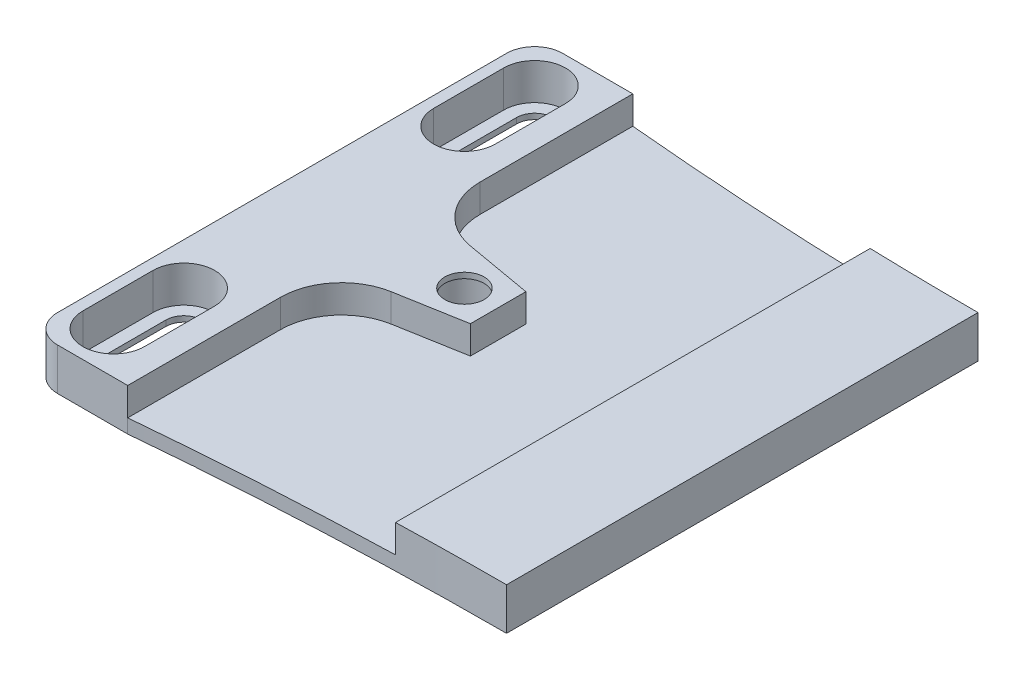
SolidWorks part; units mm, degrees
ref_plane "Front Plane" through (0, 0, 0) normal (0, 0, 1) x (1, 0, 0)
ref_plane "Top Plane" through (0, 0, 0) normal (0, 1, 0) x (1, 0, 0)
ref_plane "Right Plane" through (0, 0, 0) normal (1, 0, 0) x (0, 0, -1)
sketch "Sketch1" plane through (0, 0, 0) normal (0, 1, 0) x (1, 0, 0)
  line L1 (-82.5, -45) -> (82.5, -45)
  line L2 (-82.5, -45) -> (-82.5, 45)
  line L3 (-82.5, 45) -> (82.5, 45)
  line L4 (82.5, -45) -> (82.5, 45)
  line L5 (-82.5, -45) -> (82.5, 45) construction
  line L6 (-82.5, 45) -> (82.5, -45) construction
  point P0 (0, 0)
  dimension "D1" = 165
  dimension "D3" = 90
extrude "Boss-Extrude1" add sketch "Sketch1" along normal blind 7.5
sketch "Sketch7" plane through (0, 7.5, 0) normal (0, 1, 0) x (1, 0, 0)
  line L0 (82.5, 45) -> (-82.5, 45) construction
  line L1 (-65, 45) -> (65, 45)
  line L2 (-82.5, 0) -> (82.5, 0) construction
  line L3 (-82.5, 45) -> (-82.5, -45) construction
  line L4 (82.5, -45) -> (82.5, 45) construction
  line L5 (-65, -45) -> (65, -45)
  arc A0 (-65, 45) -> (65, 45) centre (0, 747.6667) ccw
  arc A1 (-65, -45) -> (65, -45) centre (0, -747.6667) cw
  point P5 (0, 45)
  point P14 (0, 42)
  dimension "D1" = 130
  dimension "D2" = 3
extrude "Cut-Extrude2" cut sketch "Sketch7" against normal up to next
hole_wizard "CBORE SLOT for M6 Hex Socket Head Cap Screw1" positions "Sketch8" profile "Sketch9" size "M6" standard "DIN" slot yes end condition up to next
sketch "Sketch8" plane through (0, 7.5, 0) normal (0, 1, 0) x (1, 0, 0)
  line L0 (-75, 21.8) -> (-75, 40.7) construction
  point P23 (-75, 31.25)
  point P27 (-75, -31.25)
  point P29 (75, 31.25)
  point P31 (75, -31.25)
  dimension "D1" = 18.9
  dimension "D2" = 31.25
  dimension "D3" = 31.25
  dimension "D4" = 75
  dimension "D5" = 75
sketch "Sketch9" plane through (-75, 7.5, -31.25) normal (1, 0, 0) x (0, 0, 1)
  line L0 (0, 0) -> (0, 7.5)
  line L1 (0, 7.5) -> (3.2, 7.5)
  line L3 (3.2, 7.5) -> (3.2, 6.5)
  line L4 (3.2, 6.5) -> (5.5, 6.5)
  line L5 (5.5, 6.5) -> (5.5, 0)
  line L7 (5.5, 0) -> (0, 0)
  line L11 (0, -6.35) -> (0, 107.95) construction
  dimension "Thru Hole Dia." = 6.4
  dimension "Thru Hole Depth" = 7.5
  dimension "C'Bore Dia." = 11
  dimension "C'Bore Depth" = 6.5
fillet "Fillet1" radius 5 4 edges at (82.5, 3.75, -45) (82.5, 3.75, 45) (-82.5, 3.75, 45) (-82.5, 3.75, -45)
hole_wizard "CBORE for M6 Hex Socket Head Cap Screw1" positions "Sketch10" profile "Sketch11" counterbore size "M6" standard "DIN" end condition up to next
sketch "Sketch10" plane through (0, 0, 0) normal (0, 1, 0) x (1, 0, 0)
  point P0 (-50, 0)
  point P2 (50, 0)
  dimension "D1" = 50
  dimension "D2" = 50
sketch "Sketch11" plane through (-50, 0, 0) normal (1, 0, 0) x (0, 0, -1)
  line L0 (0, 0) -> (0, 7.5)
  line L1 (0, 7.5) -> (3.5, 7.5)
  line L3 (3.5, 7.5) -> (3.5, 6.5)
  line L4 (3.5, 6.5) -> (5.5, 6.5)
  line L5 (5.5, 6.5) -> (5.5, 0)
  line L7 (5.5, 0) -> (0, 0)
  line L11 (0, -6.35) -> (0, 107.95) construction
  dimension "Thru Hole Dia." = 7
  dimension "Thru Hole Depth" = 7.5
  dimension "C'Bore Dia." = 11
  dimension "C'Bore Depth" = 6.5
sketch "Sketch12" plane through (0, 7.5, 0) normal (0, 1, 0) x (1, 0, 0)
  line L0 (-65, 45) -> (-65, 17.7837)
  line L1 (-56, 7.058) -> (-44, 4.942)
  line L2 (-44, 4.942) -> (-44, -4.942)
  line L4 (0, 42) -> (0, -42) construction
  line L5 (82.5, 0) -> (-82.5, 0) construction
  line L6 (82.5, -40) -> (82.5, 40) construction
  line L7 (-82.5, 40) -> (-82.5, -40) construction
  line L8 (44, 4.942) -> (44, -4.942)
  line L9 (56, 7.058) -> (44, 4.942)
  line L10 (65, 45) -> (65, 17.7837)
  line L11 (65, -45) -> (65, -17.7837)
  line L12 (56, -7.058) -> (44, -4.942)
  line L14 (-56, -7.058) -> (-44, -4.942)
  line L15 (-65, -45) -> (-65, -17.7837)
  line L16 (-65, -45) -> (-20, -45)
  line L17 (-20, -45) -> (-20, 45)
  line L18 (-20, 45) -> (-65, 45)
  line L19 (20, 45) -> (20, -45)
  line L20 (20, -45) -> (65, -45)
  line L21 (20, 45) -> (65, 45)
  arc A0 (-65, 17.7837) -> (-56, 7.058) centre (-54.1088, 17.7837) ccw
  circle A1 centre (-50, 0) radius 3.5 construction
  arc A2 (-65, 45) -> (65, 45) centre (0, 747.6667) ccw construction
  arc A3 (65, -45) -> (-65, -45) centre (0, -747.6667) ccw construction
  arc A4 (65, 17.7837) -> (56, 7.058) centre (54.1088, 17.7837) cw
  arc A5 (65, -17.7837) -> (56, -7.058) centre (54.1088, -17.7837) ccw
  arc A6 (-65, -17.7837) -> (-56, -7.058) centre (-54.1088, -17.7837) cw
  point P14 (-50, 6)
  point P40 (44, 0)
  point P42 (-44, 0)
  dimension "D3" = 6
  dimension "D1" = 6
  dimension "D2" = 100
  dimension "D4" = 9
  dimension "D5" = 20
extrude "Cut-Extrude3" cut sketch "Sketch12" against normal blind 5
sketch "Sketch13" plane through (0, 7.5, 0) normal (0, 1, 0) x (1, 0, 0)
  line L0 (82.5, -40) -> (82.5, 40) construction
  line L1 (0, 45) -> (82.5, 45)
  line L2 (0, 45) -> (0, -45)
  line L3 (0, -45) -> (82.5, -45)
  line L4 (82.5, 45) -> (82.5, -45)
  line L5 (77.5, 45) -> (65, 45) construction
  point P4 (0, 0)
extrude "Cut-Extrude4" cut sketch "Sketch13" against normal up to next
sketch "Sketch14" plane through (0, 7.5, 0) normal (0, 1, 0) x (1, 0, 0)
  line L0 (0, 42) -> (0, -42) construction
  line L1 (-0.5, 42.0002) -> (0, 42.0002)
  line L2 (-0.5, 42.0002) -> (-0.5, -42.0002)
  line L3 (-0.5, -42.0002) -> (0, -42.0002)
  line L4 (0, 42.0002) -> (0, -42.0002)
  arc A0 (-20, 42.2835) -> (0, 42) centre (0, 747.6667) ccw construction
  arc A1 (0, -42) -> (-20, -42.2835) centre (0, -747.6667) ccw construction
  dimension "D1" = 0.5
extrude "Cut-Extrude5" cut sketch "Sketch14" against normal up to next
